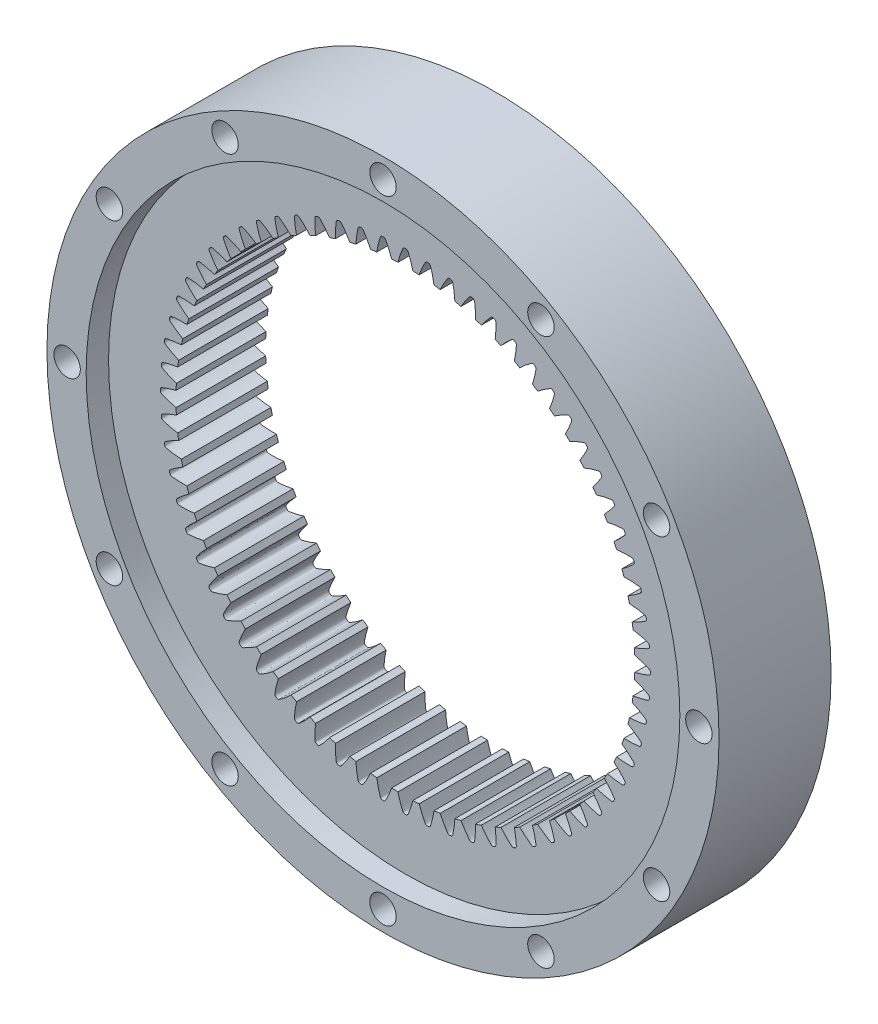
SolidWorks part; units mm, degrees
ref_plane "Front Plane" through (0, 0, 0) normal (0, 0, 1) x (1, 0, 0)
ref_plane "Top Plane" through (0, 0, 0) normal (0, 1, 0) x (1, 0, 0)
ref_plane "Right Plane" through (0, 0, 0) normal (1, 0, 0) x (0, 0, -1)
ref_axis "Axis1" through (0, 0, 55) along (0, 0, -1)
sketch "SketchRevolveRing_Gear_Follower01" plane through (0, 0, 0) normal (1, 0, 0) x (0, 0, -1)
  line L0 (0, 0) -> (25.4, 0) construction
  line L1 (-6.35, 26.0117) -> (-6.35, 38.1)
  line L2 (-6.35, 38.1) -> (6.35, 38.1)
  line L3 (6.35, 38.1) -> (6.35, 26.0117)
  line L4 (6.35, 26.0117) -> (-6.35, 26.0117)
  dimension "Side1" = 6.35
  dimension "OutsideRadius" = 38.1
  dimension "Side2" = 6.35
  dimension "MinorDiameter" = 26.0117
revolve "Ring_Gear_Follower01" add sketch "SketchRevolveRing_Gear_Follower01" angle 360 about L0
sketch "SketchToothRing_Gear_Follower01" plane through (0, 0, 0) normal (0, 0, 1) x (1, 0, 0)
  arc A0 (25.8416, -0.8773) -> (25.8416, 0.8773) centre (0, 0) ccw
  spline S0 degree 3 poles (25.8416, 0.8773) (25.9339, 0.8591) (26.0778, 0.8272) (26.276, 0.7765) (26.4414, 0.7304) (26.6175, 0.677) (26.8039, 0.6161) (27.0003, 0.5467) (27.2075, 0.4702) (27.4312, 0.3737) (27.6084, 0.3185) (27.7032, 0.2508) (27.7274, 0.2266) (27.748, 0.1994) (27.7644, 0.1694) (27.7804, 0.1272) (27.786, 0.0815) (27.7851, 0.0356) (27.7854, 0) (27.7851, -0.0356) (27.786, -0.0815) (27.7804, -0.1272) (27.7644, -0.1694) (27.748, -0.1994) (27.7274, -0.2266) (27.7032, -0.2508) (27.6084, -0.3185) (27.4312, -0.3737) (27.2075, -0.4702) (27.0003, -0.5467) (26.8039, -0.6161) (26.6175, -0.677) (26.4414, -0.7304) (26.276, -0.7765) (26.0778, -0.8272) (25.9339, -0.8591) (25.8416, -0.8773) knots 0 0 0 0 0.062937 0.098485 0.136754 0.177743 0.221452 0.267881 0.31703 0.3689 0.431324 0.438915 0.446506 0.454098 0.461689 0.46928 0.484155 0.492078 0.5 0.507922 0.515845 0.53072 0.538311 0.545902 0.553494 0.561085 0.568676 0.6311 0.68297 0.732119 0.778548 0.822257 0.863246 0.901515 0.937063 1 1 1 1
extrude "ToothExtrudeCutRing_Gear_Follower01" cut sketch "SketchToothRing_Gear_Follower01" against normal blind 6.35 and the other way blind 6.35
ref_axis "Axis2" through (41.91, 0, 0) along (-1, 0, 0)
ref_plane "Plane1" through (0, 0, 0) normal (0, 0, -1) x (1, 0, 0)
pattern_circular "PatternRing_Gear_Follower01" count 68 every 5.294 about axis through (0, 0, 55) along (0, 0, -1) of "ToothExtrudeCutRing_Gear_Follower01"
sketch "AuxiliarySketchRing_Gear_Follower01" plane through (0, 0, 0) normal (0, 0, 1) x (1, 0, 0)
  circle A0 centre (0, 0) radius 26.8 construction
  circle A1 centre (0, 0) radius 25.1837 construction
  circle A2 centre (0, 0) radius 27.7853 construction
  circle A3 centre (0, 0) radius 26.0117 construction
  dimension "PitchDiameter" = 53.6
  dimension "BaseDiameter" = 50.3675
  dimension "MajorDiameter" = 55.5706
  dimension "MinorDiameter" = 52.0235
sketch "Sketch1" plane through (0, 0, 6.35) normal (0, 0, 1) x (1, 0, 0)
  circle A0 centre (0, 0) radius 33.655 construction
  circle A1 centre (0, 0) radius 34.925 construction
  circle A2 centre (0, 0) radius 28.575 construction
  circle A3 centre (0, 0) radius 33.655
  dimension "D1" = 67.31
  dimension "D2" = 69.85
  dimension "D3" = 57.15
extrude "Cut-Extrude1" cut sketch "Sketch1" against normal blind 2.54
sketch "Sketch2" plane through (0, 0, 6.35) normal (0, 0, 1) x (1, 0, 0)
  line L0 (0, 0) -> (0, 41.5527) construction
  circle A0 centre (0, 0) radius 35.814 construction
  circle A1 centre (0, 35.814) radius 1.5
  circle A2 centre (17.907, 31.0158) radius 1.5
  circle A3 centre (31.0158, 17.907) radius 1.5
  circle A4 centre (35.814, 0) radius 1.5
  circle A5 centre (31.0158, -17.907) radius 1.5
  circle A6 centre (17.907, -31.0158) radius 1.5
  circle A7 centre (0, -35.814) radius 1.5
  circle A8 centre (-17.907, -31.0158) radius 1.5
  circle A9 centre (-31.0158, -17.907) radius 1.5
  circle A10 centre (-35.814, 0) radius 1.5
  circle A11 centre (-31.0158, 17.907) radius 1.5
  circle A12 centre (-17.907, 31.0158) radius 1.5
  point P30 (0, 0)
  dimension "D1" = 71.628
  dimension "D2" = 3
  dimension "D3" = 12
extrude "Cut-Extrude2" cut sketch "Sketch2" against normal through all
